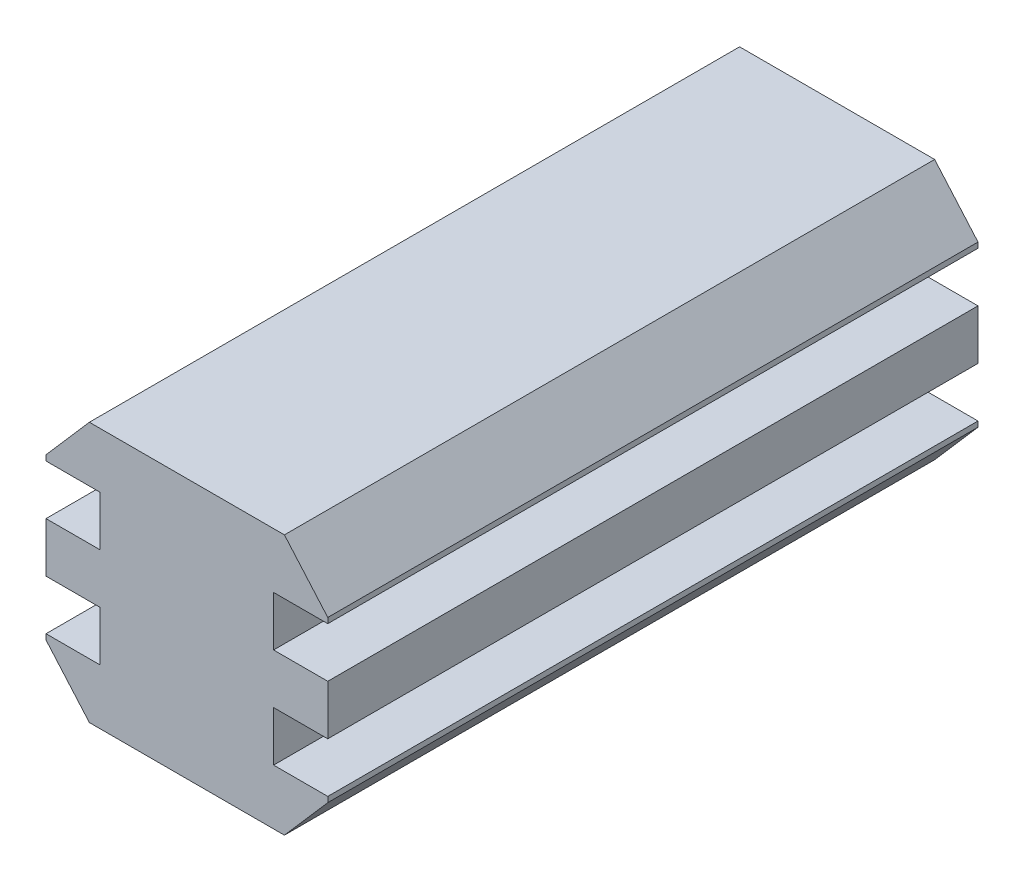
SolidWorks part; units mm, degrees
material "PE Alta Densidade"
ref_plane "Plano frontal" through (0, 0, 0) normal (0, 0, 1) x (1, 0, 0)
ref_plane "Plano superior" through (0, 0, 0) normal (0, 1, 0) x (1, 0, 0)
ref_plane "Plano direito" through (0, 0, 0) normal (1, 0, 0) x (0, 0, -1)
sketch "Esboço1" plane through (0, 0, 0) normal (0, 0, 1) x (1, 0, 0)
  line L0 (-4.5, -6) -> (4.5, -6)
  line L1 (-4.5, -6) -> (-6.5, -3.7)
  line L2 (6.5, -3.7) -> (6.5, -3.45)
  line L3 (6.5, -3.45) -> (4, -3.45)
  line L4 (4, -3.45) -> (4, -1.15)
  line L5 (4, -1.15) -> (6.5, -1.15)
  line L6 (6.5, -1.15) -> (6.5, 1.15)
  line L7 (4, 1.15) -> (6.5, 1.15)
  line L8 (4, 3.45) -> (4, 1.15)
  line L9 (6.5, 3.45) -> (4, 3.45)
  line L10 (6.5, 3.7) -> (6.5, 3.45)
  line L11 (4.5, -6) -> (6.5, -3.7)
  line L12 (4.5, 6) -> (6.5, 3.7)
  line L13 (0, 14.388) -> (0, -9.624) construction
  line L14 (-4.5, 6) -> (4.5, 6)
  line L15 (-6.5, -3.7) -> (-6.5, -3.45)
  line L16 (-6.5, -3.45) -> (-4, -3.45)
  line L17 (-4, -3.45) -> (-4, -1.15)
  line L18 (-4, -1.15) -> (-6.5, -1.15)
  line L19 (-6.5, -1.15) -> (-6.5, 1.15)
  line L20 (-4.5, 6) -> (-6.5, 3.7)
  line L21 (-6.5, 3.7) -> (-6.5, 3.45)
  line L22 (-6.5, 3.45) -> (-4, 3.45)
  line L23 (-4, 3.45) -> (-4, 1.15)
  line L24 (-4, 1.15) -> (-6.5, 1.15)
  line L25 (-8.8286, 0) -> (11.4625, 0) construction
  point P0 (0, 0)
  point P1 (6.5, -6)
  point P17 (-6.5, -6)
  point P31 (6.5, 0)
  point P33 (0, -6)
  dimension "D1" = 12
  dimension "D2" = 13
  dimension "D3" = 2.3
  dimension "D4" = 2.3
  dimension "D5" = 0.25
  dimension "D6" = 8
  dimension "D7" = 9
extrude "Ressalto-extrusão1" add sketch "Esboço1" along normal blind 30
